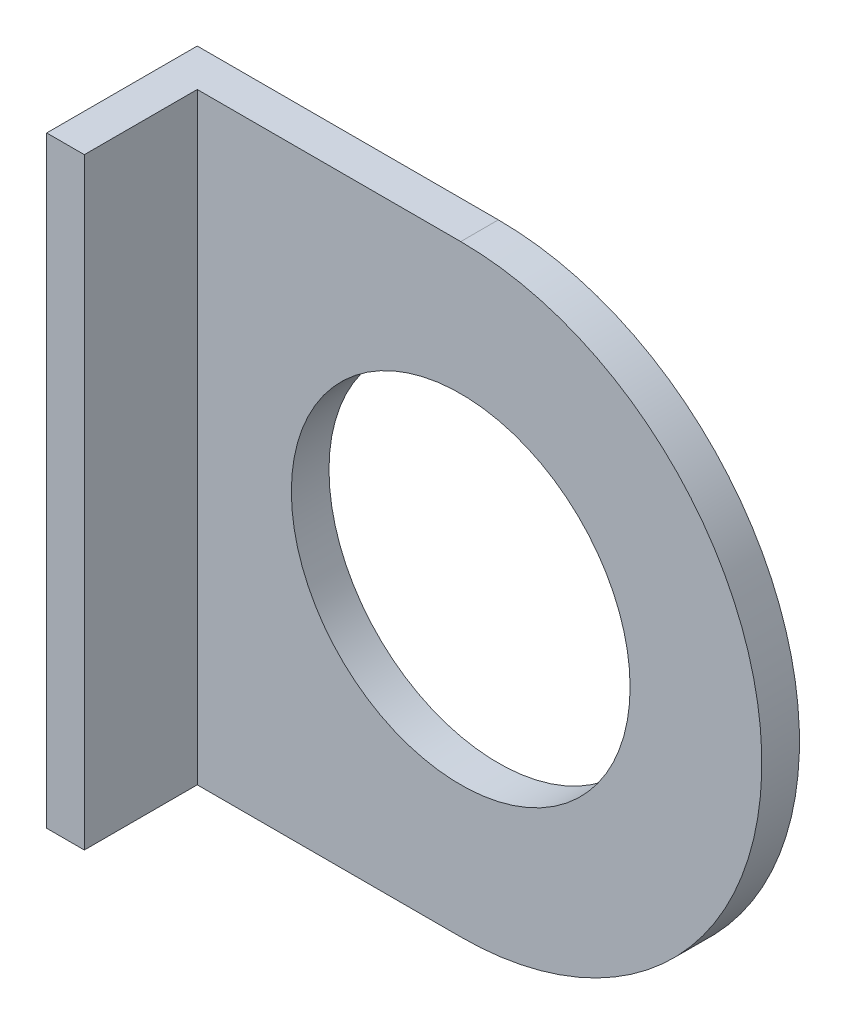
SolidWorks part; units mm, degrees
ref_plane "Front Plane" through (0, 0, 0) normal (0, 0, 1) x (1, 0, 0)
ref_plane "Top Plane" through (0, 0, 0) normal (0, 1, 0) x (1, 0, 0)
ref_plane "Right Plane" through (0, 0, 0) normal (1, 0, 0) x (0, 0, -1)
sketch "Sketch1" plane through (0, 0, 309.2672) normal (0, 0, 1) x (1, 0, 0)
  line L0 (51.9768, -201.4847) -> (51.9768, -150.6847)
  line L1 (51.9768, -150.6847) -> (77.3768, -150.6847)
  line L2 (77.3768, -201.4847) -> (51.9768, -201.4847)
  arc A0 (77.3768, -150.6847) -> (77.3768, -201.4847) centre (77.3768, -176.0847) cw
  circle A10 centre (77.3768, -176.0847) radius 14.2875
  arc A11 (40.8458, -174.0872) -> (12.3078, -174.0872) centre (26.5768, -174.8147) ccw construction
  arc A12 (40.8458, -174.0872) -> (12.3078, -174.0872) centre (26.5768, -174.8147) ccw construction
  point P0 (77.443, -201.4847)
  point P2 (0, 0)
  point P6 (52.9714, -201.4853)
  dimension "D10" = 28.575
  dimension "D2" = 25.4
  dimension "D13" = 50.8
extrude "Boss-Extrude1" add sketch "Sketch1" along normal blind 3.175
sketch "Sketch2" plane through (0, 0, 312.4422) normal (0, 0, 1) x (1, 0, 0)
  line L0 (77.3768, -150.6847) -> (51.9768, -150.6847) construction
  line L1 (55.1518, -150.6847) -> (51.9768, -150.6847)
  line L2 (55.1518, -150.6847) -> (55.1518, -201.4847)
  line L3 (55.1518, -201.4847) -> (51.9768, -201.4847)
  line L4 (51.9768, -150.6847) -> (51.9768, -201.4847)
  dimension "D1" = 3.175
extrude "Boss-Extrude2" add sketch "Sketch2" along normal blind 9.525
